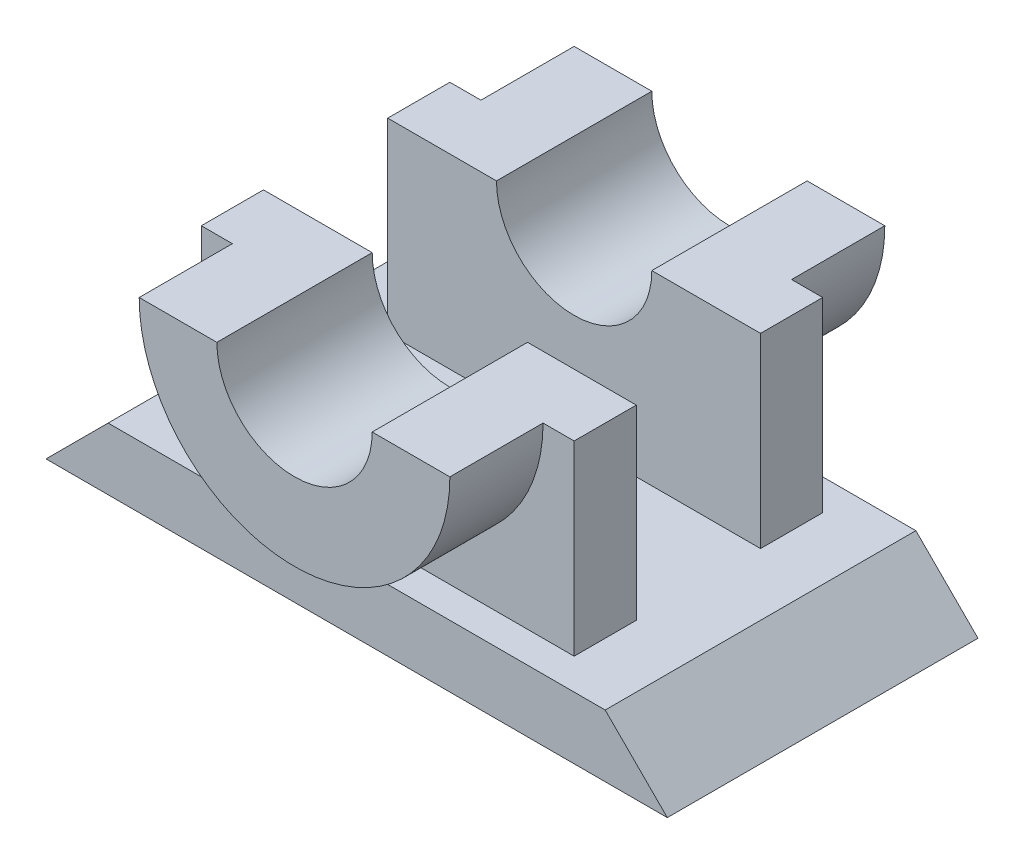
SolidWorks part; units mm, degrees
material "AISI 1020"
ref_plane "Front Plane" through (0, 0, 0) normal (0, 0, 1) x (1, 0, 0)
ref_plane "Top Plane" through (0, 0, 0) normal (0, 1, 0) x (1, 0, 0)
ref_plane "Right Plane" through (0, 0, 0) normal (1, 0, 0) x (0, 0, -1)
sketch "Sketch1" plane through (0, 0, 0) normal (0, 1, 0) x (1, 0, 0)
  line L1 (-50, 25) -> (50, 25)
  line L2 (-50, 25) -> (-50, -25)
  line L3 (-50, -25) -> (50, -25)
  line L4 (50, 25) -> (50, -25)
  line L5 (-50, 25) -> (50, -25) construction
  line L6 (-50, -25) -> (50, 25) construction
  point P0 (0, 0)
  dimension "D1" = 50
  dimension "D2" = 100
extrude "Boss-Extrude1" add sketch "Sketch1" along normal blind 10
chamfer "Chamfer1" distance 10 angle 45 1 edges at (-50, 10, 0)
chamfer "Chamfer2" distance 10 angle 45 1 edges at (50, 10, 0)
sketch "Sketch2" plane through (0, 0, 0) normal (0, 1, 0) x (1, 0, 0)
  line L1 (40, -25) -> (40, 25) construction
  line L2 (-30, -10) -> (30, -10)
  line L3 (-30, -10) -> (-30, -20)
  line L4 (-30, -20) -> (30, -20)
  line L5 (30, -10) -> (30, -20)
  line L6 (-30, -10) -> (30, -20) construction
  line L7 (-30, -20) -> (30, -10) construction
  line L8 (-40, -25) -> (40, -25) construction
  line L9 (-53.166, 0) -> (62.2741, 0) construction
  line L10 (30, 10) -> (30, 20)
  line L11 (-30, 20) -> (30, 20)
  line L12 (-30, 10) -> (-30, 20)
  line L13 (-30, 10) -> (30, 10)
  point P2 (0, -15)
  point P16 (0, 0)
  point P17 (0, 0)
  point P18 (0, 0)
  dimension "D1" = 60
  dimension "D2" = 10
  dimension "D3" = 10
  dimension "D4" = 5
extrude "Boss-Extrude3" add sketch "Sketch2" along normal blind 40
sketch "Sketch4" plane through (0, 0, 20) normal (0, 0, 1) x (1, 0, 0)
  line L0 (0, 0) -> (0, 48.3834) construction
  line L1 (-30, 40) -> (30, 40) construction
  line L2 (-12.5, 40) -> (12.5, 40)
  arc A0 (-12.5, 40) -> (12.5, 40) centre (0, 40) ccw
  dimension "D1" = 12.5
extrude "Cut-Extrude1" cut sketch "Sketch4" against normal blind 64
sketch "Sketch10" plane through (0, 0, 20) normal (0, 0, 1) x (1, 0, 0)
  line L0 (0, 0) -> (0, 56.7932) construction
  line L1 (-30, 40) -> (18.4493, 40) construction
  line L2 (12.5, 40) -> (30, 40) construction
  line L3 (-25, 40) -> (-12.5, 40)
  line L4 (12.5, 40) -> (25, 40)
  arc A0 (-25, 40) -> (25, 40) centre (0, 40) ccw
  arc A1 (-12.5, 40) -> (12.5, 40) centre (0, 40) ccw
  arc A2 (-12.5, 40) -> (12.5, 40) centre (0, 40) ccw construction
  dimension "D1" = 25
extrude "Boss-Extrude5" add sketch "Sketch10" along normal blind 15
sketch "Sketch11" plane through (0, 0, -20) normal (0, 0, -1) x (-1, 0, 0)
  line L0 (0, 0) -> (0, 57.4916) construction
  line L1 (-30, 40) -> (30, 40) construction
  line L2 (-12.5, 40) -> (-25, 40)
  line L3 (12.5, 40) -> (25, 40)
  arc A0 (-25, 40) -> (25, 40) centre (0, 40) ccw
  arc A1 (-12.5, 40) -> (12.5, 40) centre (0, 40) ccw
  arc A2 (-12.5, 40) -> (12.5, 40) centre (0, 40) ccw construction
  dimension "D1" = 25
extrude "Boss-Extrude6" add sketch "Sketch11" along normal blind 15
